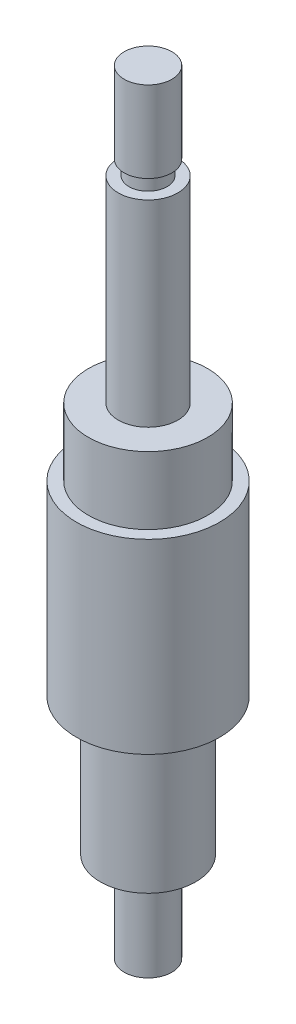
SolidWorks part; units mm, degrees
ref_plane "Front Plane" through (0, 0, 0) normal (0, 0, 1) x (1, 0, 0)
ref_plane "Top Plane" through (0, 0, 0) normal (0, 1, 0) x (1, 0, 0)
ref_plane "Right Plane" through (0, 0, 0) normal (1, 0, 0) x (0, 0, -1)
sketch "Sketch1" plane through (0, 0, 0) normal (0, 0, 1) x (1, 0, 0)
  line L0 (0, 0) -> (0, 67.2246) construction
  line L1 (0, 0) -> (2, 0)
  line L2 (2, 0) -> (2, 7.5612)
  line L3 (2, 7.5612) -> (4, 7.5612)
  line L4 (4, 7.5612) -> (4, 19.0549)
  line L5 (4, 19.0549) -> (6, 19.0549)
  line L6 (6, 19.0549) -> (6, 34.6718)
  line L7 (5, 40.3337) -> (2.5, 40.3337)
  line L8 (2.5, 40.3337) -> (2.5, 56.8337)
  line L9 (2, 64.8337) -> (0, 64.8337)
  line L10 (2, 64.8337) -> (2, 58.0337)
  line L11 (1.6, 56.8337) -> (2.5, 56.8337)
  line L12 (0, 64.8337) -> (0, 0)
  line L13 (5, 40.3337) -> (5, 34.6718)
  line L14 (5, 34.6718) -> (6, 34.6718)
  line L15 (2, 58.0337) -> (1.6, 58.0337)
  line L16 (1.6, 58.0337) -> (1.6, 56.8337)
  point P18 (0.9686, 60.9913)
  dimension "D1" = 12
  dimension "D2" = 8
  dimension "D3" = 5
  dimension "D4" = 4
  dimension "D5" = 3.2
  dimension "D6" = 16.5
  dimension "D7" = 10
  dimension "D8" = 1.2
  dimension "D9" = 8
revolve "Revolve1" add sketch "Sketch1" angle 360 about L0
